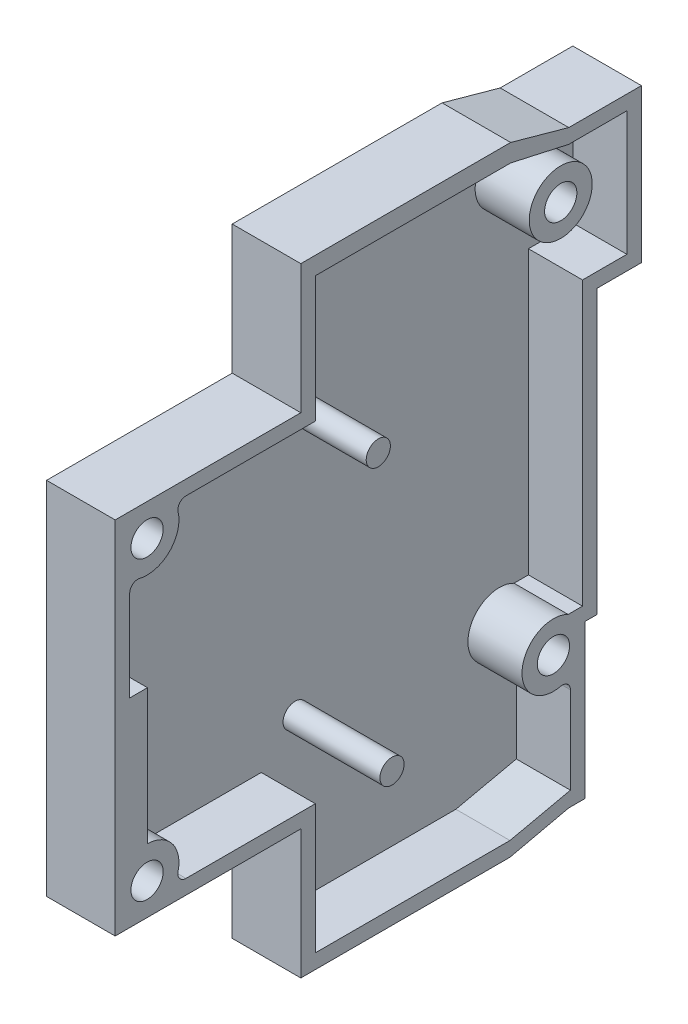
SolidWorks part; units mm, degrees
ref_plane "Спереди" through (0, 0, 0) normal (0, 0, 1) x (1, 0, 0)
ref_plane "Сверху" through (0, 0, 0) normal (0, 1, 0) x (1, 0, 0)
ref_plane "Справа" through (0, 0, 0) normal (1, 0, 0) x (0, 0, -1)
sketch "Эскиз1" plane through (0, 0, 0) normal (1, 0, 0) x (0, 0, -1)
  line L0 (-6.85, 22.325) -> (-6.85, 38.325)
  line L1 (-29.85, -22.325) -> (29.85, -22.325) construction
  line L2 (-29.85, -22.325) -> (-29.85, 22.325)
  line L3 (-29.85, 22.325) -> (29.85, 22.325) construction
  line L4 (29.85, -22.325) -> (29.85, 22.325) construction
  line L5 (-29.85, -22.325) -> (29.85, 22.325) construction
  line L6 (-29.85, 22.325) -> (29.85, -22.325) construction
  line L7 (-6.85, 38.325) -> (19.15, 38.325)
  line L8 (19.15, 38.325) -> (26.35, 36.325)
  line L9 (26.35, 36.325) -> (35.35, 36.325)
  line L10 (35.35, 36.325) -> (35.35, 17.325)
  line L11 (35.35, 17.325) -> (29.85, 17.325)
  line L12 (-29.85, 22.325) -> (-6.85, 22.325)
  line L13 (29.85, -22.325) -> (29.85, 17.325) construction
  line L14 (-6.85, -22.325) -> (-6.85, -38.325)
  line L15 (-6.85, -38.325) -> (19.0618, -38.325)
  line L16 (19.0618, -38.325) -> (26.35, -36.675)
  line L17 (26.35, -36.675) -> (28.35, -36.675)
  line L18 (28.35, -36.675) -> (28.35, -17.675)
  line L19 (28.35, -17.675) -> (29.85, -17.675)
  line L20 (-29.85, -22.325) -> (-6.85, -22.325)
  line L21 (29.85, 17.325) -> (29.85, -17.675)
  line L22 (-5.05, -20.525) -> (-5.05, -36.525)
  line L23 (-5.05, -36.525) -> (19.0618, -36.525)
  line L24 (19.0618, -36.525) -> (26.55, -34.875)
  line L25 (26.55, -34.875) -> (26.55, -15.875) construction
  line L26 (26.55, -15.875) -> (28.05, -15.875)
  line L27 (28.05, -15.875) -> (28.05, 19.125)
  line L28 (28.05, 19.125) -> (33.55, 19.125)
  line L29 (33.55, 19.125) -> (33.55, 34.525)
  line L30 (33.55, 34.525) -> (26.35, 34.525)
  line L31 (26.35, 34.525) -> (19.15, 36.125)
  line L32 (19.15, 36.125) -> (-5.05, 36.125)
  line L33 (-5.05, 36.125) -> (-5.05, 20.525)
  line L34 (-5.05, 20.525) -> (-28.05, 20.525) construction
  line L35 (-28.05, 20.525) -> (-28.05, -20.525) construction
  line L36 (-28.05, -20.525) -> (-5.05, -20.525) construction
  line L37 (-21.0854, 20.525) -> (-5.05, 20.525)
  line L38 (-28.05, 13.5604) -> (-28.05, 2.325)
  line L39 (-21.0854, -20.525) -> (-5.05, -20.525)
  line L40 (26.55, -15.875) -> (26.2687, -15.875)
  line L41 (26.55, -24.0999) -> (26.55, -34.875)
  line L42 (-25.85, 2.325) -> (-25.85, -14.4253)
  line L43 (-28.05, 2.325) -> (-25.85, 2.325)
  line L44 (-28.05, 2.325) -> (-28.05, -16.375) construction
  line L45 (-28.05, -16.375) -> (-25.85, -16.375) construction
  line L46 (-25.85, 2.325) -> (-25.85, -16.375) construction
  line L47 (-28.05, 2.325) -> (-25.85, -16.375) construction
  line L48 (-28.05, -16.375) -> (-25.85, 2.325) construction
  circle A0 centre (-0.85, -16.475) radius 1.5
  circle A1 centre (-2.55, 18.525) radius 1.5
  circle A2 centre (25.35, 28.825) radius 3.9
  circle A3 centre (24.45, -19.325) radius 3.9 construction
  circle A4 centre (-25.9, -18.375) radius 3.95 construction
  circle A5 centre (-25.9, 18.375) radius 3.95 construction
  arc A6 (-22.0581, 19.2927) -> (-26.8177, 14.5331) centre (-25.9, 18.375) cw
  arc A7 (-25.85, -14.4253) -> (-22.0581, -19.2927) centre (-25.9, -18.375) cw
  arc A8 (25.3255, -23.1255) -> (26.2687, -15.875) centre (24.45, -19.325) cw
  circle A9 centre (25.35, 28.825) radius 2
  circle A10 centre (-25.9, 18.375) radius 2
  circle A11 centre (-25.9, -18.375) radius 2
  circle A12 centre (24.45, -19.325) radius 2
  arc A13 (-22.0581, 19.2927) -> (-21.0854, 20.525) centre (-21.0854, 19.525) cw
  arc A14 (-26.8177, 14.5331) -> (-28.05, 13.5604) centre (-27.05, 13.5604) ccw
  arc A15 (25.3255, -23.1255) -> (26.55, -24.0999) centre (25.55, -24.0999) cw
  arc A17 (-22.0581, -19.2927) -> (-21.0854, -20.525) centre (-21.0854, -19.525) ccw
  point P4 (0, 0)
  point P15 (-5.05, -20.525)
  point P21 (-28.05, 20.525)
  point P22 (-5.05, 20.525)
  point P23 (-5.05, 36.125)
  point P24 (19.15, 36.125)
  point P25 (26.35, 34.525)
  point P26 (33.55, 34.525)
  point P27 (33.55, 19.125)
  point P28 (28.05, 19.125)
  point P29 (28.05, -15.875)
  point P30 (26.55, -15.875)
  point P31 (26.55, -34.875)
  point P32 (19.0618, -36.525)
  point P33 (-5.05, -36.525)
  point P34 (-5.05, -20.525)
  point P74 (-22.5864, 20.525)
  point P77 (-28.05, 15.0614)
  point P80 (26.55, -22.6113)
  point P83 (-28.05, -15.0614)
  point P86 (-22.5864, -20.525)
  point P91 (-26.95, -7.025)
  dimension "D31" = 3
  dimension "D34" = 3
  dimension "D37" = 8.2
  dimension "D39" = 7.8
  dimension "D41" = 7.8
  dimension "D42" = 7.9
  dimension "D43" = 7.9
  dimension "D44" = 4
  dimension "D45" = 4
  dimension "D46" = 4
  dimension "D47" = 4
  dimension "D48" = 1
  dimension "D1" = 59.7
  dimension "D2" = 44.65
  dimension "D3" = 16
  dimension "D4" = 26
  dimension "D5" = 5
  dimension "D6" = 19
  dimension "D7" = 23
  dimension "D8" = 9
  dimension "D9" = 5.5
  dimension "D10" = 1.5
  dimension "D11" = 35
  dimension "D12" = 19
  dimension "D13" = 1.8
  dimension "D14" = 24.8
  dimension "D15" = 1.8
  dimension "D16" = 1.8
  dimension "D17" = 1.8
  dimension "D18" = 2.2
  dimension "D19" = 1.8
  dimension "D20" = 1.8
  dimension "D21" = 1.8
  dimension "D22" = 1.8
  dimension "D23" = 1.8
  dimension "D24" = 1.8
  dimension "D25" = 1.8
  dimension "D27" = 4
  dimension "D28" = 1.8
  dimension "D29" = 1.8
  dimension "D30" = 1.8
  dimension "D32" = 4.2
  dimension "D33" = 35
  dimension "D35" = 2
  dimension "D36" = 2.5
  dimension "D38" = 5.7
  dimension "D40" = 19
  dimension "D49" = 20
extrude "Бобышка-Вытянуть2" add sketch "Эскиз1" along normal blind 8.5 contours A2 A9 | L21 L11 L10 L9 L8 L7 L0 L12 L2 L20 L14 L15 L16 L17 L18 L19 A17 A7 L38 A14 A6 A13 L37 L33 L32 L31 L30 L29 L28 L27 L26 A8 A15 L41 L24 L23 L22 L39 A12 A11 A10 region at (0, 30.325, 5.8437) region at (0, 28.825, -21.5603)
extrude "Бобышка-Вытянуть3" add sketch "Эскиз1<6>" along normal blind 1.8 contours A7 A17 L39 L22 L23 L24 L41 A15 A8 L26 L27 L28 L29 L30 L31 L32 L33 L37 A13 A6 A14 L38 A0 A1 A2 region at (0, 0.6688, -4.3982)
sketch "Эскиз1<6>" plane through (0, 0, 0) normal (1, 0, 0) x (0, 0, -1) same geometry as "Эскиз1"
extrude "Бобышка-Вытянуть4" add sketch "Эскиз1<7>" along normal blind 13.8 contours A1 | A0 region at (0, -16.475, 0.85) region at (0, 18.525, 2.55)
sketch "Эскиз1<7>" plane through (0, 0, 0) normal (1, 0, 0) x (0, 0, -1) same geometry as "Эскиз1"
